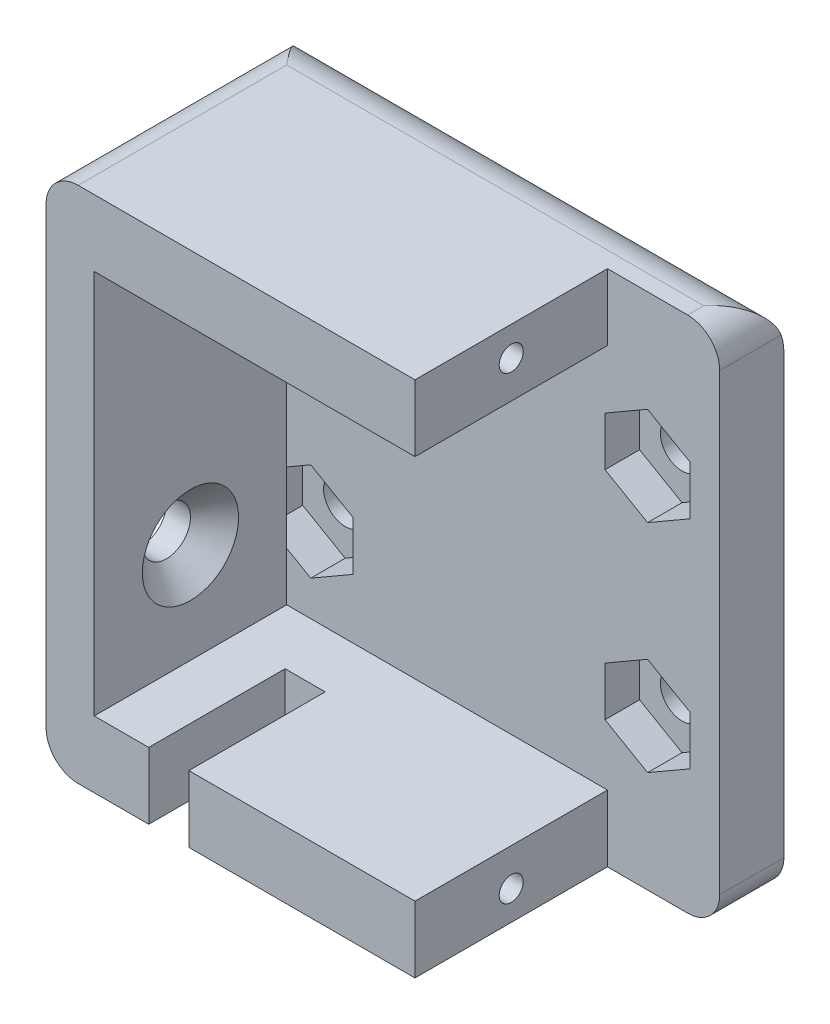
SolidWorks part; units mm, degrees
ref_plane "Спереди" through (0, 0, 0) normal (0, 0, 1) x (1, 0, 0)
ref_plane "Сверху" through (0, 0, 0) normal (0, 1, 0) x (1, 0, 0)
ref_plane "Справа" through (0, 0, 0) normal (1, 0, 0) x (0, 0, -1)
sketch "Эскиз1" plane through (0, 0, 0) normal (0, 0, 1) x (1, 0, 0)
  line L1 (-15, -16.15) -> (15, -16.15)
  line L2 (-15, -16.15) -> (-15, 16.15)
  line L3 (-15, 16.15) -> (15, 16.15)
  line L4 (15, -16.15) -> (15, 16.15)
  line L5 (-15, -16.15) -> (15, 16.15) construction
  line L6 (-15, 16.15) -> (15, -16.15) construction
  point P0 (0, 0)
  dimension "D1" = 30
  dimension "D2" = 32.3
extrude "тело" add sketch "Эскиз1" along normal blind 4
sketch "Эскиз2" plane through (0, 0, 4) normal (0, 0, 1) x (1, 0, 0)
  line L0 (8, 16.15) -> (-15, 16.15)
  line L1 (15, 16.15) -> (-15, 16.15) construction
  line L2 (-15, 16.15) -> (-15, -16.15)
  line L3 (-15, -16.15) -> (8, -16.15)
  line L4 (-15, -16.15) -> (15, -16.15) construction
  line L5 (8, -16.15) -> (8, -12)
  line L6 (8, -12) -> (-12, -12)
  line L8 (-12, 12) -> (8, 12)
  line L9 (8, 12) -> (8, 16.15)
  line L12 (-12, 12) -> (-12, -12)
  dimension "D1" = 20
  dimension "D3" = 24
  dimension "D4" = 3
extrude "крепление сервы" add sketch "Эскиз2" along normal blind 12
sketch "Эскиз4" plane through (-12, 0, 0) normal (1, 0, 0) x (0, 0, -1)
  line L0 (-10, 12) -> (-10, -12) construction
  line L1 (-16, 12) -> (-4, 12) construction
  line L2 (-16, -12) -> (-4, -12) construction
  circle A0 centre (-10, -5.77) radius 1.5
  dimension "D1" = 3
  dimension "D2" = 5.77
extrude "отверстие под выход второй оси" cut sketch "Эскиз4" against normal through all
chamfer "Фаска1" distance 1.5 angle 45 1 edges at (-12, -4.27, 10)
sketch "Эскиз3" plane through (8, 0, 0) normal (1, 0, 0) x (0, 0, -1)
  line L0 (-10, 16.15) -> (-10, 12) construction
  line L1 (-16, 16.15) -> (-4, 16.15) construction
  line L2 (-16, 12) -> (-4, 12) construction
  circle A0 centre (-10, 14.32) radius 0.75
  point P17 (-9, -5.77)
  dimension "D1" = 1.5
  dimension "D2" = 2.32
extrude "отверстие под саморез" cut sketch "Эскиз3" against normal blind 10
mirror "Зеркальное отражение2" about plane through (0, 0, 0) normal (0, 1, 0) of "отверстие под саморез"
sketch "Эскиз5" plane through (0, -16.15, 0) normal (0, -1, 0) x (1, 0, 0)
  line L0 (-15, 16) -> (8, 16) construction
  line L1 (-8.6, 16) -> (-6.1, 16)
  line L2 (-8.6, 16) -> (-8.6, 7.5)
  line L3 (-8.6, 7.5) -> (-6.1, 7.5)
  line L4 (-6.1, 16) -> (-6.1, 7.5)
  dimension "D1" = 2.5
  dimension "D2" = 3.4
  dimension "D3" = 8.5
extrude "паз для проводов" cut sketch "Эскиз5" against normal up to surface (4.15 mm away) up to face at (-2, -12, 10)
sketch "Эскиз6" plane through (0, 0, 0) normal (0, 0, -1) x (-1, 0, 0)
  line L0 (0, 16.15) -> (0, -16.15) construction
  line L1 (-15, 16.15) -> (15, 16.15) construction
  line L2 (15, -16.15) -> (-15, -16.15) construction
  line L4 (-14.25, -14.25) -> (14.25, -14.25) construction
  line L5 (-14.25, -14.25) -> (-14.25, 14.25) construction
  line L6 (-14.25, 14.25) -> (14.25, 14.25) construction
  line L7 (14.25, -14.25) -> (14.25, 14.25) construction
  line L8 (-14.25, -14.25) -> (14.25, 14.25) construction
  line L9 (-14.25, 14.25) -> (14.25, -14.25) construction
  circle A0 centre (-14.25, 14.25) radius 1.1
  circle A1 centre (14.25, 14.25) radius 1.1
  circle A2 centre (14.25, -14.25) radius 1.1
  circle A3 centre (-14.25, -14.25) radius 1.1
  point P6 (0, 0)
  dimension "D1" = 2.2
  dimension "D3" = 28.5
extrude "крепление камеры (большой)" [suppressed] cut sketch "Эскиз6" against normal through all
chamfer "Фаска2" [suppressed] distance 1 angle 45
fillet "Скругление1" radius 2 4 edges at (15, 16.15, 2) (15, -16.15, 2) (-15, -16.15, 8) (-15, 16.15, 8)
sketch "Эскиз7" plane through (0, 0, 0) normal (0, 0, -1) x (-1, 0, 0)
  line L1 (-10.5, 6.75) -> (10.5, 6.75) construction
  line L2 (-10.5, 6.75) -> (-10.5, -6.75) construction
  line L3 (-10.5, -6.75) -> (10.5, -6.75) construction
  line L4 (10.5, 6.75) -> (10.5, -6.75) construction
  line L5 (-10.5, 6.75) -> (10.5, -6.75) construction
  line L6 (-10.5, -6.75) -> (10.5, 6.75) construction
  circle A0 centre (10.5, 6.75) radius 1.35
  circle A1 centre (-10.5, 6.75) radius 1.35
  circle A2 centre (-10.5, -6.75) radius 1.35
  circle A3 centre (10.5, -6.75) radius 1.35
  point P0 (0, 0)
  dimension "D3" = 2.7
  dimension "D1" = 21
  dimension "D2" = 13.5
extrude "Отверстия под крепеж с верхней частью корпуса" cut sketch "Эскиз7" against normal up to next
sketch "Эскиз8" plane through (0, 0, 4) normal (0, 0, 1) x (1, 0, 0)
  line L0 (0, 16.15) -> (0, -16.15) construction
  line L1 (10.5, 9.81) -> (7.85, 8.28)
  line L2 (7.85, 8.28) -> (7.85, 5.22)
  line L3 (7.85, 5.22) -> (10.5, 3.69)
  line L4 (10.5, 3.69) -> (13.15, 5.22)
  line L5 (13.15, 5.22) -> (13.15, 8.28)
  line L6 (13.15, 8.28) -> (10.5, 9.81)
  line L7 (-15, 0) -> (15, 0) construction
  line L8 (15, -16.15) -> (15, 16.15) construction
  line L9 (-15, -16.15) -> (-15, 16.15) construction
  line L10 (-15, 16.15) -> (15, 16.15) construction
  line L11 (-15, -16.15) -> (15, -16.15) construction
  line L12 (-13.15, 8.28) -> (-10.5, 9.81)
  line L13 (-13.15, 5.22) -> (-13.15, 8.28)
  line L14 (-10.5, 3.69) -> (-13.15, 5.22)
  line L15 (-7.85, 5.22) -> (-10.5, 3.69)
  line L16 (-7.85, 8.28) -> (-7.85, 5.22)
  line L17 (-10.5, 9.81) -> (-7.85, 8.28)
  line L18 (-10.5, -9.81) -> (-7.85, -8.28)
  line L19 (-7.85, -8.28) -> (-7.85, -5.22)
  line L20 (-7.85, -5.22) -> (-10.5, -3.69)
  line L21 (-10.5, -3.69) -> (-13.15, -5.22)
  line L22 (-13.15, -5.22) -> (-13.15, -8.28)
  line L23 (-13.15, -8.28) -> (-10.5, -9.81)
  line L24 (13.15, -8.28) -> (10.5, -9.81)
  line L25 (13.15, -5.22) -> (13.15, -8.28)
  line L26 (10.5, -3.69) -> (13.15, -5.22)
  line L27 (7.85, -5.22) -> (10.5, -3.69)
  line L28 (7.85, -8.28) -> (7.85, -5.22)
  line L29 (10.5, -9.81) -> (7.85, -8.28)
  circle A1 centre (10.5, 6.75) radius 2.65 construction
  circle A2 centre (-10.5, 6.75) radius 2.65 construction
  circle A3 centre (-10.5, -6.75) radius 2.65 construction
  circle A4 centre (10.5, -6.75) radius 2.65 construction
  dimension "D1" = 5.3
extrude "Углубления под гайки" cut sketch "Эскиз8" against normal blind 2.15 contours L12 L17 L16 L15 L14 L13 | L1 L2 L3 L4 L5 L6 | L24 L29 L28 L27 L26 L25 | L18 L19 L20 L21 L22 L23
fillet "Скругление2" radius 3 1 edges at (0, 16.15, 0) tangent propagation no
